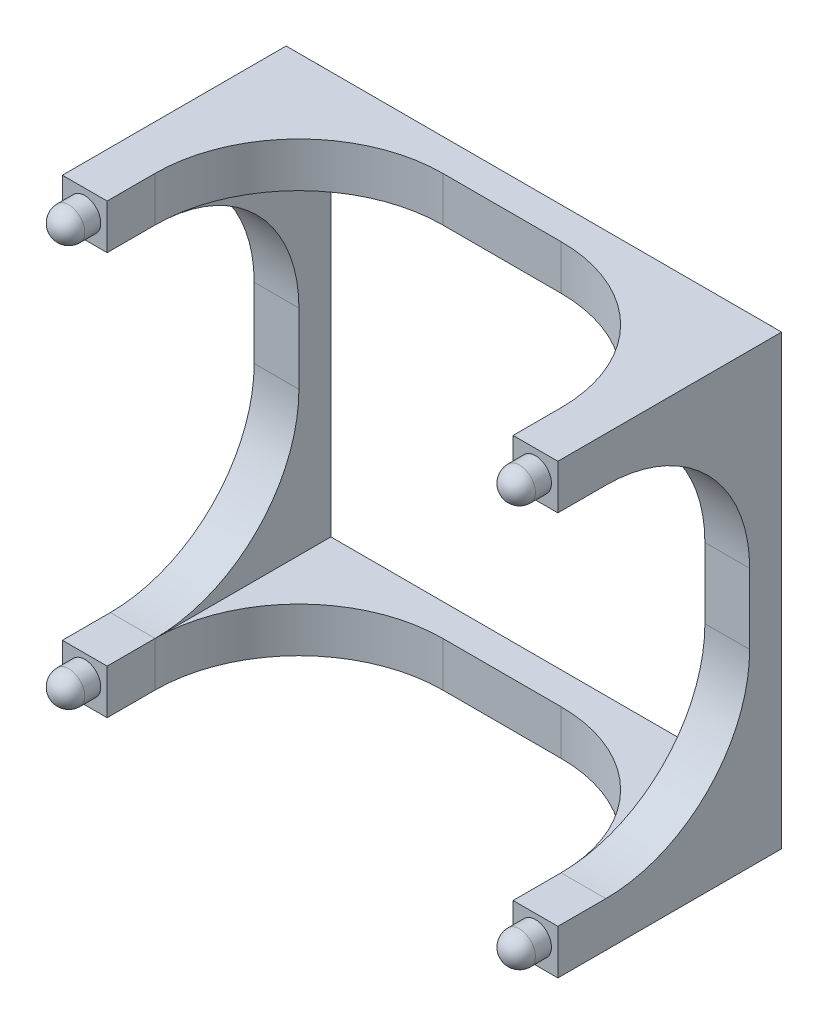
SolidWorks part; units mm, degrees
ref_plane "Ebene vorne" through (0, 0, 0) normal (0, 0, 1) x (1, 0, 0)
ref_plane "Ebene oben" through (0, 0, 0) normal (0, 1, 0) x (1, 0, 0)
ref_plane "Ebene rechts" through (0, 0, 0) normal (1, 0, 0) x (0, 0, -1)
sketch "Skizze1" plane through (0, 0, 0) normal (0, 0, 1) x (1, 0, 0)
  line L1 (-77.5, -70) -> (77.5, -70)
  line L2 (-77.5, -70) -> (-77.5, 70)
  line L3 (-77.5, 70) -> (77.5, 70)
  line L4 (77.5, -70) -> (77.5, 70)
  line L5 (-77.5, -70) -> (77.5, 70) construction
  line L6 (-77.5, 70) -> (77.5, -70) construction
  line L7 (-63.5, -56) -> (63.5, -56)
  line L8 (-63.5, -56) -> (-63.5, 56)
  line L9 (-63.5, 56) -> (63.5, 56)
  line L10 (63.5, -56) -> (63.5, 56)
  line L11 (-63.5, -56) -> (63.5, 56) construction
  line L12 (-63.5, 56) -> (63.5, -56) construction
  point P0 (0, 0)
  point P6 (0, 0)
extrude "Aufsatz-Linear austragen1" add sketch "Skizze1" along normal blind 10
sketch "Skizze2" plane through (0, 0, 10) normal (0, 0, 1) x (1, 0, 0)
  line L0 (-77.5, -70) -> (77.5, -70) construction
  line L1 (-63.5, 56) -> (-77.5, 56)
  line L2 (-63.5, 56) -> (-63.5, 70)
  line L3 (-63.5, 70) -> (-77.5, 70)
  line L4 (-77.5, 56) -> (-77.5, 70)
  line L5 (63.5, 56) -> (77.5, 56)
  line L6 (63.5, 56) -> (63.5, 70)
  line L7 (63.5, 70) -> (77.5, 70)
  line L8 (77.5, 56) -> (77.5, 70)
  line L9 (63.5, -56) -> (77.5, -56)
  line L10 (63.5, -56) -> (63.5, -70)
  line L11 (63.5, -70) -> (77.5, -70)
  line L12 (77.5, -56) -> (77.5, -70)
  line L13 (77.5, -70) -> (77.5, 70) construction
  line L14 (-77.5, 70) -> (-77.5, -70) construction
  line L15 (-63.5, -56) -> (-77.5, -56)
  line L16 (-63.5, -56) -> (-63.5, -70)
  line L17 (-63.5, -70) -> (-77.5, -70)
  line L18 (-77.5, -56) -> (-77.5, -70)
extrude "Aufsatz-Linear austragen2" add sketch "Skizze2" along normal blind 60
sketch "Skizze3" plane through (0, 0, 70) normal (0, 0, 1) x (1, 0, 0)
  circle A0 centre (-70.5, -62.6732) radius 5
  circle A1 centre (70.5, -62.6732) radius 5
  circle A2 centre (70.5, 63) radius 5
  circle A3 centre (-70.5, 63) radius 5
extrude "Aufsatz-Linear austragen3" add sketch "Skizze3" along normal blind 10
fillet "Verrundung1" radius 5 4 edges at (75.5, 63, 80) (75.5, -62.6732, 80) (-65.5, 63, 80) (-65.5, -62.6732, 80)
sketch3d "3D-Skizze3"
  point P4 (-63.5, -63, 70)
  point P6 (-63.5, -63, 70)
  point P8 (-63.5, -63, 10)
  point P13 (63.5, -63, 70)
fillet "Verrundung3" radius 45 1 edges at (-63.5, -63, 10)
fillet "Verrundung4" radius 45 1 edges at (-70.5, -56, 10)
fillet "Verrundung6" radius 45 3 edges at (-63.5, 63, 10) (63.5, 63, 10) (63.5, -63, 10)
fillet "Verrundung7" radius 45 3 edges at (70.5, -56, 10) (-70.5, 56, 10) (70.5, 56, 10)
sketch "Skizze9" plane through (0, 0, 0) normal (0, 0, -1) x (-1, 0, 0)
  circle A0 centre (70.5, -62.6732) radius 5
  circle A1 centre (70.5, 63) radius 5
  circle A2 centre (-70.5, 63) radius 5
  circle A3 centre (-70.5, -62.6732) radius 5
extrude "Aufsatz-Linear austragen4" add sketch "Skizze9" along normal blind 5
fillet "Verrundung8" radius 5 4 edges at (65.5, 63, -5) (-75.5, 63, -5) (-75.5, -62.6732, -5) (65.5, -62.6732, -5)
